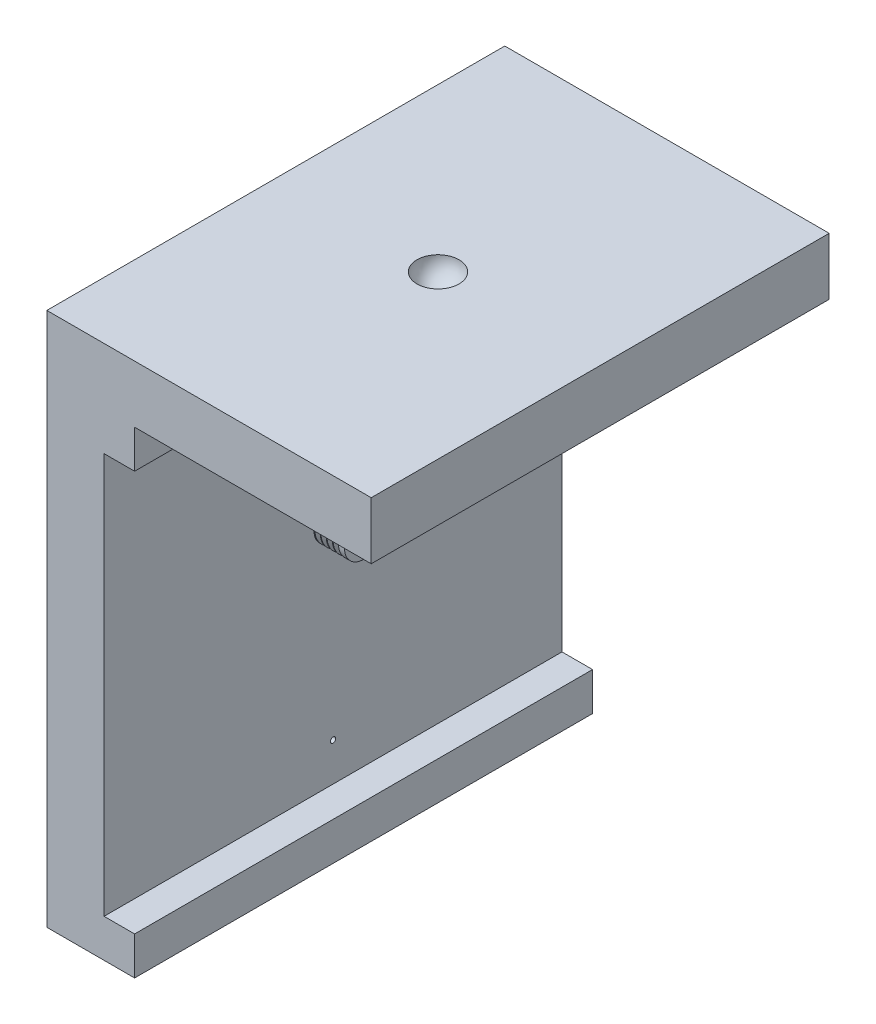
SolidWorks part; units mm, degrees
ref_plane "Front Plane" through (0, 0, 0) normal (0, 0, 1) x (1, 0, 0)
ref_plane "Top Plane" through (0, 0, 0) normal (0, 1, 0) x (1, 0, 0)
ref_plane "Right Plane" through (0, 0, 0) normal (1, 0, 0) x (0, 0, -1)
sketch "Sketch1" plane through (0, 0, 0) normal (0, 0, 1) x (1, 0, 0)
  line L0 (0, 0) -> (0, -70)
  line L1 (0, 0) -> (42.5, 0)
  line L2 (0, -70) -> (7.5, -70)
  line L3 (42.5, 0) -> (42.5, -7.5)
  line L4 (42.5, -7.5) -> (7.5, -7.5)
  line L5 (7.5, -7.5) -> (7.5, -70)
extrude "Boss-Extrude1" add sketch "Sketch1" along normal blind 60
sketch "Sketch3" plane through (0, 0, 0) normal (-1, 0, 0) x (0, 0, 1)
  line L1 (60, 0) -> (60, -70) construction
  line L2 (60, -60) -> (0, -60) construction
  line L3 (0, 0) -> (0, -70) construction
  circle A0 centre (30, -60) radius 0.35
extrude "Cut-Extrude1" cut sketch "Sketch3" against normal through all contours A0
sketch "Sketch5" plane through (7.5, 0, 0) normal (1, 0, 0) x (0, 0, -1)
  line L0 (-60, -70) -> (-60, -7.5) construction
  line L1 (0, -70) -> (-60, -70)
  line L2 (0, -70) -> (0, -65)
  line L3 (0, -65) -> (-60, -65)
  line L4 (-60, -70) -> (-60, -65)
  line L5 (0, -70) -> (0, -7.5) construction
  line L6 (-60, -7.5) -> (0, -7.5)
  line L7 (-60, -7.5) -> (-60, -12.5)
  line L8 (-60, -12.5) -> (0, -12.5)
  line L9 (0, -7.5) -> (0, -12.5)
  dimension "D1" = 5
  dimension "D2" = 5
extrude "Boss-Extrude2" add sketch "Sketch5" along normal blind 4
sketch "Sketch6" plane through (7.5, 0, 0) normal (1, 0, 0) x (0, 0, -1)
  line L0 (-30, -60) -> (-30, -35) construction
  circle A0 centre (-30, -35) radius 2.5
extrude "Boss-Extrude3" add sketch "Sketch6" along normal blind 4
thread "Thread1" pitch 0.7937 method cut profile "Thread Profile1" start angle 0, offset 0, length 5, pitch 0.7937, diameter 5
ref_plane "Plane1" through (11.5, -35, 32.5) normal (0, -1, 0) x (0, 0, 1)
sketch "Thread Profile1" plane through (11.5, -35, 32.5) normal (0, -1, 0) x (0, 0, 1)
  line L0 (0, 0) -> (0, 0.7937) construction
  line L11 (0, 0) -> (0, 0.6945)
  line L12 (0, 0.6945) -> (-0.4296, 0.4465)
  line L13 (-0.4296, 0.4465) -> (-0.4296, 0.248)
  line L15 (-0.4296, 0.248) -> (0, 0)
  line L17 (-0.4296, 0.3473) -> (0, 0.3473) construction
  point P2 (0, 0)
  dimension "Pitch" = 0.7937
  dimension "Profile_Angle" = 60
  dimension "Profile_Land" = 0.1984
  dimension "Profile_Height" = 0.4296
sketch "Sketch7" plane through (0, 0, 0) normal (0, 1, 0) x (1, 0, 0)
  line L0 (18.5, -30) -> (24, -30) construction
  line L1 (18.5, -30) -> (24, -30)
  arc A1 (24, -30) -> (18.5, -30) centre (21.25, -30) cw
revolve "Cut-Revolve1" cut sketch "Sketch7" angle 360 about L0
